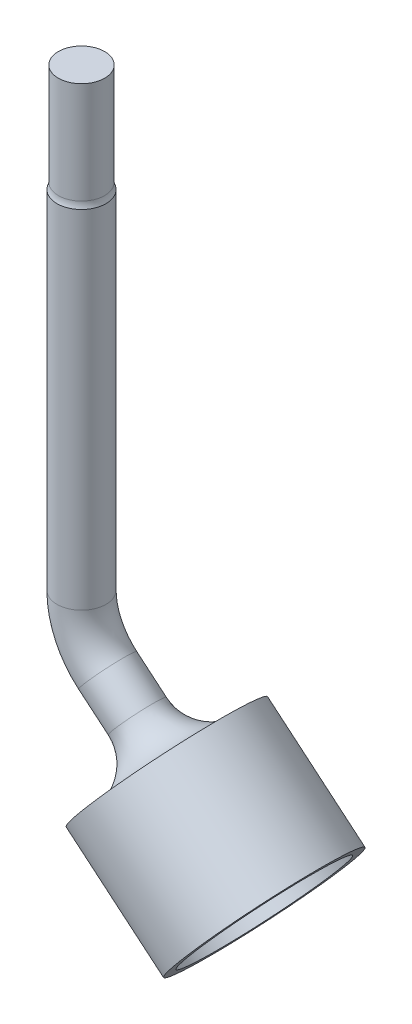
SolidWorks part; units mm, degrees
note: '?' marks a value the reader was unsure of.
material "Alloy Steel"
ref_plane "Front Plane" through (0, 0, 0) normal (0, 0, 1) x (1, 0, 0)
ref_plane "Top Plane" through (0, 0, 0) normal (0, 1, 0) x (1, 0, 0)
ref_plane "Right Plane" through (0, 0, 0) normal (1, 0, 0) x (0, 0, -1)
sketch "Sketch1" plane through (0, 0, 0) normal (0, 1, 0) x (1, 0, 0)
  circle A0 centre (0, 0) radius 3.175
  dimension "D1" = 6.35
extrude "Boss-Extrude1" add sketch "Sketch1" along normal blind 40
sketch "Sketch2" plane through (0, 0, 0) normal (0, -1, 0) x (1, 0, 0)
  circle A0 centre (0, 0) radius 3.175
  circle A1 centre (0, 0) radius 3.175 construction
sketch "Sketch3" plane through (0, 0, 0) normal (0, 0, 1) x (1, 0, 0)
  line L0 (0, 0) -> (0, -5)
  line L1 (3.4024, -12.2966) -> (11.0629, -18.7244)
  line L3 (0, -5) -> (9.525, -5) construction
  arc A0 (0, -5) -> (3.4024, -12.2966) centre (9.525, -5) ccw
  dimension "D1" = 9.525
  dimension "D2" = 130
  dimension "D3" = 5
  dimension "D4" = 10
sweep "Sweep1" add profiles "Sketch2" path "Sketch3"
sketch "Sketch5" plane through (15.712, -13.1839, 0) normal (0.766, -0.6428, 0) x (0, 0, -1)
  circle A0 centre (0, -7.2327) radius 11
  circle A1 centre (0, -7.2327) radius 3.175 construction
  dimension "D1" = 22
extrude "Boss-Extrude2" add sketch "Sketch5" along normal blind 1.5
sketch "Sketch4" plane through (16.861, -14.1481, 0) normal (0.766, -0.6428, 0) x (0, 0, -1)
  circle A0 centre (0, -7.2327) radius 11
  circle A1 centre (0, -7.2327) radius 7.9375 construction
  circle A2 centre (0, -7.2327) radius 9.652
  circle A3 centre (0, -7.2327) radius 11 construction
  circle A4 centre (0, -7.2327) radius 6.4375 construction
  circle M9 centre (0, -7.2327) radius 11
  dimension "D1" = 1.5
  dimension "D2" = 19.304
  dimension "D3" = 15.875
extrude "Boss-Extrude3" add sketch "Sketch4" along normal blind 15 contours A2 M9 | A1
ref_axis "Axis1" through (18.955, -25.3467, 0) along (-0.766, 0.6428, 0)?
ref_plane "Plane1" through (-4.6491, -5.5405, 0) normal (0.6428, 0.766, 0) x (-0.766, 0.6428, 0)
sketch "Sketch6" plane through (0, 40, 0) normal (0, 1, 0) x (1, 0, 0)
  circle A0 centre (0, 0) radius 3
  circle A1 centre (0, 0) radius 3.175 construction
  dimension "D1" = 6
extrude "Boss-Extrude4" add sketch "Sketch6" along normal blind 14
hole_wizard "M3x0.5 Tapped Hole1" [suppressed] positions "Sketch8" profile "Sketch7" tap size "M3x0.5" standard "ANSI Metric"
sketch "Sketch8" plane through (0, 45, 0) normal (0, 1, 0) x (1, 0, 0)
  point P0 (0, 0)
sketch "Sketch7" plane through (0, 45, 0) normal (1, 0, 0) x (0, 0, 1)
  line L0 (0, 0) -> (0, 8.2511)
  line L1 (0, 8.2511) -> (1.25, 7.5)
  line L2 (1.25, 7.5) -> (1.25, 0)
  line L5 (1.25, 0) -> (0, 0)
  line L10 (0, 8.2511) -> (-1.25, 7.5) construction
  line L11 (0, -6.35) -> (0, 107.95) construction
  dimension "Tap Drill Dia." = 2.5
  dimension "Tap Drill Depth" = 7.5
  dimension "Drill Angle" = 118
cosmetic thread "Hole Thread1" [suppressed] parameters "D1"=6, "D2"=3
fillet "Fillet1" radius 2 1 edges at (0, 40, 3)
ref_axis "Axis2" through (18.955, -25.3467, 0) along (-0.766, 0.6428, 0)?
ref_plane "Plane2" through (0, 0, 0) normal (0, 0, 1) x (-0.766, 0.6428, 0)
ref_axis "Axis3" through (13.7159, -17.8963, 0) along (0.6428, 0.766, 0)?
ref_plane "Plane3" through (16.861, -14.1481, 0) normal (-0.766, 0.6428, 0) x (0.6428, 0.766, 0)
ref_plane "Plane4" through (-4.6491, -5.5405, 0) normal (0.6428, 0.766, 0) x (-0.766, 0.6428, 0)
ref_axis "Axis4" through (12.212, -19.6886, 10.8862) along (0, 0, -1)?
fillet "Fillet2" radius 5 1 edges at (11.0629, -18.7244, -3.175)
